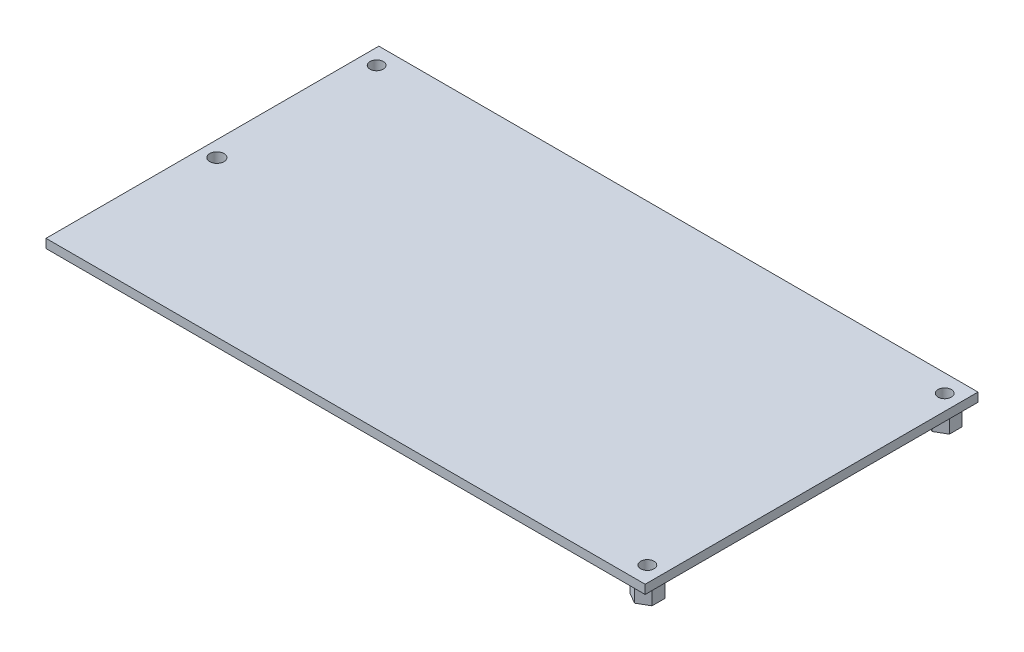
SolidWorks part; units mm, degrees
ref_plane "Спереди" through (0, 0, 0) normal (0, 0, 1) x (1, 0, 0)
ref_plane "Сверху" through (0, 0, 0) normal (0, 1, 0) x (1, 0, 0)
ref_plane "Справа" through (0, 0, 0) normal (1, 0, 0) x (0, 0, -1)
sketch "Эскиз1" plane through (0, 0, 0) normal (0, 1, 0) x (1, 0, 0)
  line L0 (0, 0) -> (135, 0)
  line L1 (0, 0) -> (0, 75)
  line L2 (135, 0) -> (135, 75)
  line L3 (0, 75) -> (135, 75)
  line L4 (3.5, 71) -> (131.5, 71) construction
  line L5 (3.5, 71) -> (3.5, 4) construction
  line L6 (131.5, 71) -> (131.5, 4) construction
  line L7 (3.5, 4) -> (131.5, 4) construction
  line L8 (67.5, 71) -> (67.5, 4) construction
  line L9 (131.5, 37.5) -> (3.5, 37.5) construction
  line L10 (67.5, 75) -> (67.5, 0) construction
  line L11 (135, 37.5) -> (0, 37.5) construction
  circle A0 centre (3.5, 71) radius 1.5
  circle A1 centre (3.5, 35) radius 1.6
  circle A2 centre (131.5, 71) radius 1.5
  circle A3 centre (131.5, 4) radius 1.5
  dimension "D5" = 3
  dimension "D6" = 3.2
  dimension "D7" = 3
  dimension "D8" = 3
  dimension "D9" = 36
  dimension "D1" = 75
  dimension "D2" = 135
  dimension "D3" = 67
  dimension "D4" = 128
extrude "Бобышка-Вытянуть1" add sketch "Эскиз1" along normal blind 2
sketch "Эскиз2" plane through (0, 0, 0) normal (0, -1, 0) x (1, 0, 0)
  line L0 (3.5, -32.1132) -> (3.5, -37.8868) construction
  line L1 (3.5, -37.8868) -> (6, -36.4434)
  line L2 (6, -36.4434) -> (6, -33.5566)
  line L3 (6, -33.5566) -> (3.5, -32.1132)
  line L4 (3.5, -32.1132) -> (1, -33.5566)
  line L5 (1, -33.5566) -> (1, -36.4434)
  line L6 (1, -36.4434) -> (3.5, -37.8868)
  line L7 (3.5, -73.8868) -> (6, -72.4434)
  line L8 (6, -72.4434) -> (6, -69.5566)
  line L9 (6, -69.5566) -> (3.5, -68.1132)
  line L10 (3.5, -68.1132) -> (1, -69.5566)
  line L11 (1, -69.5566) -> (1, -72.4434)
  line L12 (1, -72.4434) -> (3.5, -73.8868)
  line L13 (131.5, -6.8868) -> (134, -5.4434)
  line L14 (134, -5.4434) -> (134, -2.5566)
  line L15 (134, -2.5566) -> (131.5, -1.1132)
  line L16 (131.5, -1.1132) -> (129, -2.5566)
  line L17 (129, -2.5566) -> (129, -5.4434)
  line L18 (129, -5.4434) -> (131.5, -6.8868)
  line L19 (129, -72.4434) -> (131.5, -73.8868)
  line L20 (131.5, -73.8868) -> (134, -72.4434)
  line L21 (134, -72.4434) -> (134, -69.5566)
  line L22 (134, -69.5566) -> (131.5, -68.1132)
  line L23 (131.5, -68.1132) -> (129, -69.5566)
  line L24 (129, -69.5566) -> (129, -72.4434)
  line L25 (3.5, -68.1132) -> (3.5, -73.8868) construction
  line L26 (131.5, -1.1132) -> (131.5, -6.8868) construction
  line L27 (131.5, -68.1132) -> (131.5, -73.8868) construction
  circle A0 centre (3.5, -35) radius 2.5 construction
  circle A1 centre (3.5, -71) radius 2.5 construction
  circle A2 centre (131.5, -4) radius 2.5 construction
  circle A3 centre (131.5, -71) radius 2.5 construction
  circle A4 centre (3.5, -35) radius 1.6 construction
  circle A5 centre (3.5, -35) radius 1.6 construction
  dimension "D1" = 5
  dimension "D2" = 5
  dimension "D3" = 5
  dimension "D4" = 5
extrude "Бобышка-Вытянуть2" add sketch "Эскиз2" along normal blind 4
sketch "Эскиз3" plane through (0, 0, 0) normal (0, 1, 0) x (1, 0, 0)
  circle A0 centre (3.5, 71) radius 1.5 construction
  circle A2 centre (131.5, 4) radius 1.5 construction
  circle A3 centre (131.5, 71) radius 1.5 construction
  circle A4 centre (3.5, 71) radius 1.5
  circle A5 centre (3.5, 35) radius 1.6 construction
  circle A6 centre (131.5, 4) radius 1.5
  circle A7 centre (131.5, 71) radius 1.5
  circle A8 centre (3.5, 35) radius 1.6
extrude "Вырез-Вытянуть1" cut sketch "Эскиз3" against normal through all
sketch "Эскиз4" plane through (0, 2, 0) normal (0, 1, 0) x (1, 0, 0)
  line L0 (3.5, 71) -> (3.5, 35) construction
  dimension "D1" = 36
